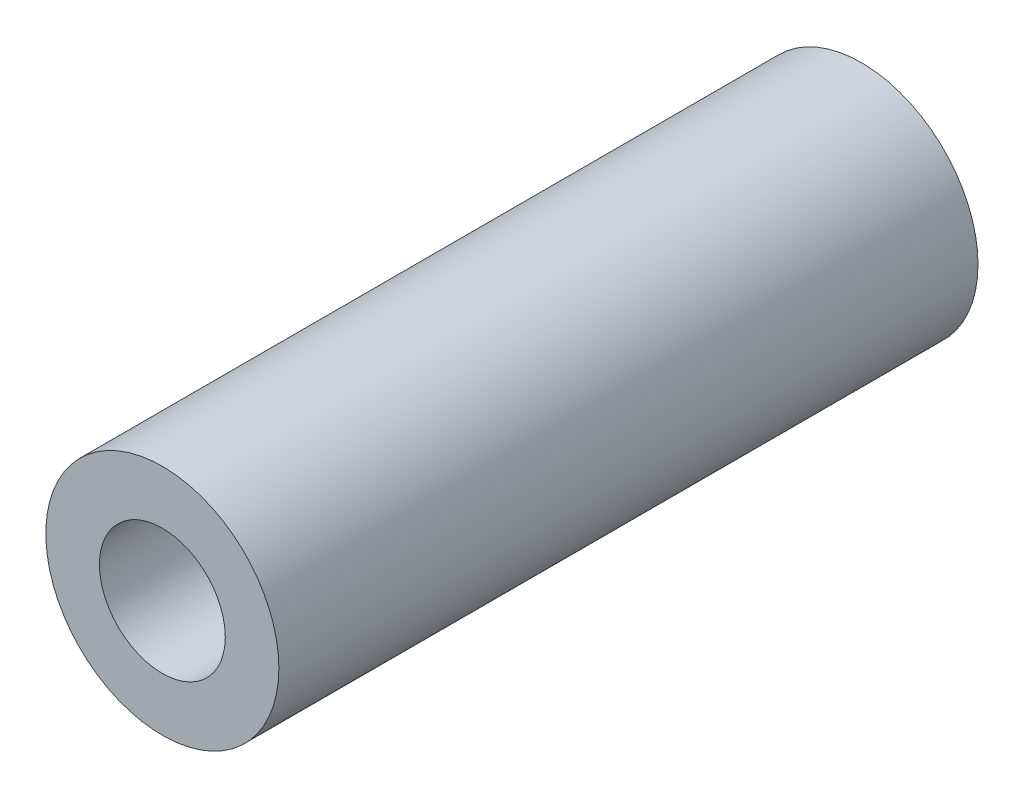
SolidWorks part; units mm, degrees
ref_plane "Alzado" through (0, 0, 0) normal (0, 0, 1) x (1, 0, 0)
ref_plane "Planta" through (0, 0, 0) normal (0, 1, 0) x (1, 0, 0)
ref_plane "Vista lateral" through (0, 0, 0) normal (1, 0, 0) x (0, 0, -1)
sketch "Croquis1" plane through (0, 0, 0) normal (0, 0, 1) x (1, 0, 0)
  circle A0 centre (0, 0) radius 2.5
  dimension "D1" = 5
extrude "Saliente-Extruir1" add sketch "Croquis1" along normal blind 15
sketch "Croquis2" plane through (0, 0, 15) normal (0, 0, 1) x (1, 0, 0)
  line L0 (0, 2.5) -> (0, -2.5) construction
  line L1 (-2.5, 0) -> (2.5, 0) construction
  circle A0 centre (0, 0) radius 2.5 construction
hole_wizard "Taladro de margen para M2.51" positions "Croquis5" profile "Croquis3" hole size "M2.5" standard "ISO" end condition through all
sketch "Croquis5" plane through (0, 0, 15) normal (0, 0, 1) x (1, 0, 0)
  point P0 (0, 0)
sketch "Croquis3" plane through (0, 0, 15) normal (1, 0, 0) x (0, -1, 0)
  line L0 (0, 0) -> (0, 15)
  line L1 (0, 15) -> (1.35, 15)
  line L2 (1.35, 15) -> (1.35, 0)
  line L5 (1.35, 0) -> (0, 0)
  line L11 (0, -6.35) -> (0, 107.95) construction
  dimension "Diámetro de taladro hasta el siguiente" = 2.7
  dimension "Profundidad de taladro hasta el siguiente" = 15
